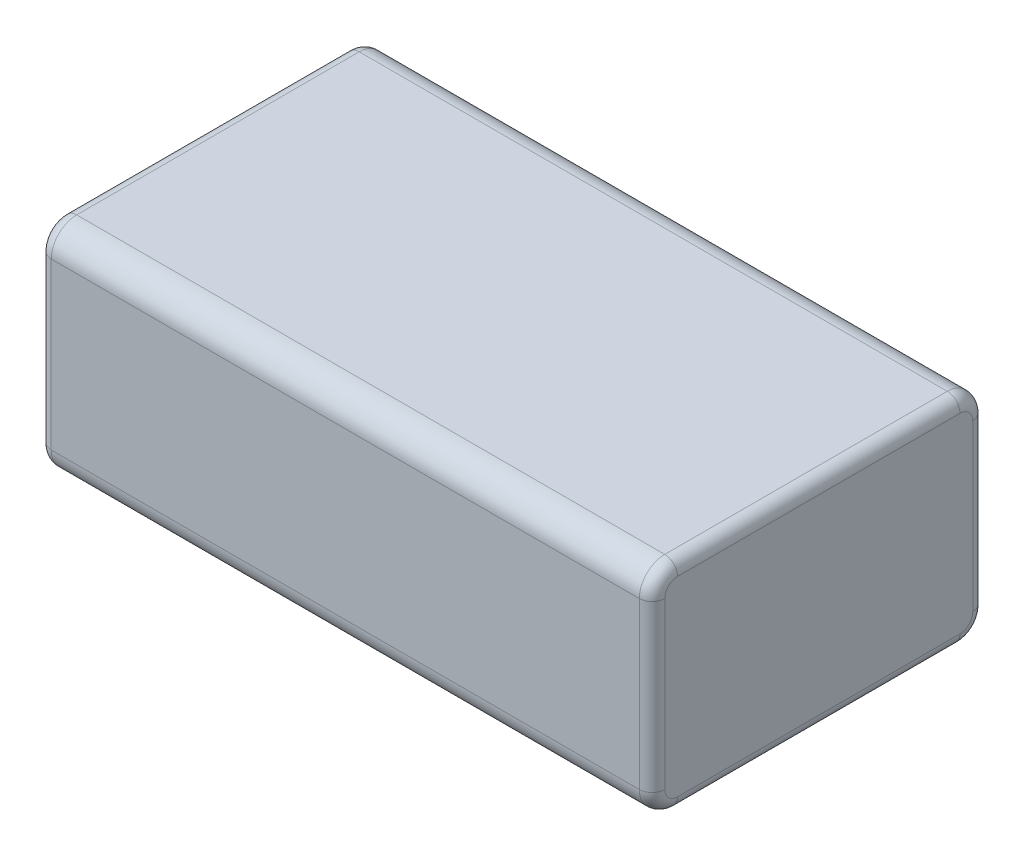
SolidWorks part; units mm, degrees
ref_plane "Front Plane" through (0, 0, 0) normal (0, 0, 1) x (1, 0, 0)
ref_plane "Top Plane" through (0, 0, 0) normal (0, 1, 0) x (1, 0, 0)
ref_plane "Right Plane" through (0, 0, 0) normal (1, 0, 0) x (0, 0, -1)
sketch "Sketch1" plane through (0, 0, 0) normal (0, 1, 0) x (1, 0, 0)
  line L1 (24.075, -13.085) -> (-24.075, -13.085)
  line L2 (24.075, -13.085) -> (24.075, 13.085)
  line L3 (24.075, 13.085) -> (-24.075, 13.085)
  line L4 (-24.075, -13.085) -> (-24.075, 13.085)
  line L5 (24.075, -13.085) -> (-24.075, 13.085) construction
  line L6 (24.075, 13.085) -> (-24.075, -13.085) construction
  point P0 (0, 0)
  dimension "D1" = 48.15
  dimension "D2" = 26.17
extrude "Boss-Extrude1" add sketch "Sketch1" along normal blind 16.98
fillet "Fillet1" radius 2 4 edges at (0, 0, -13.085) (0, 0, 13.085) (0, 16.98, -13.085) (0, 16.98, 13.085)
fillet "Fillet2" radius 1 16 edges at (-24.075, 16.3942, 12.4992) (-24.075, 16.98, 0) (-24.075, 16.3942, -12.4992) (-24.075, 8.49, -13.085) (-24.075, 0.5858, -12.4992) (-24.075, 0, 0) (-24.075, 0.5858, 12.4992) (24.075, 16.3942, 12.4992) (24.075, 16.98, 0) (24.075, 16.3942, -12.4992) (24.075, 8.49, -13.085) (24.075, 0.5858, -12.4992) (24.075, 0, 0) (24.075, 0.5858, 12.4992) (-24.075, 8.49, 13.085) (24.075, 8.49, 13.085)
sketch "Sketch2" plane through (-24.075, 0, 0) normal (-1, 0, 0) x (0, 0, 1)
  line L1 (4.5107, 13.1244) -> (0.6107, 10.8727)
  line L2 (0.6107, 10.8727) -> (0.6107, 6.3694)
  line L3 (0.6107, 6.3694) -> (4.5107, 4.1177)
  line L4 (4.5107, 4.1177) -> (8.4107, 6.3694)
  line L5 (8.4107, 6.3694) -> (8.4107, 10.8727)
  line L6 (8.4107, 10.8727) -> (4.5107, 13.1244)
  circle A0 centre (-5.4512, 8.49) radius 3.665
  circle A1 centre (4.5107, 8.621) radius 3.665
  circle A2 centre (4.5107, 8.621) radius 3.9 construction
  circle A3 centre (-5.4512, 8.49) radius 3.4
  point P12 (0, 0)
  dimension "D1" = 7.33
  dimension "D2" = 7.33
extrude "Boss-Extrude2" add sketch "Sketch2" along normal blind 3
fillet "Fillet6" radius 0.3 7 edges at (-27.075, 8.621, 8.1757) (-27.075, 8.621, 8.4107) (-27.075, 11.9985, 6.4607) (-27.075, 11.9985, 2.5607) (-27.075, 8.621, 0.6107) (-27.075, 5.2435, 6.4607) (-27.075, 5.2435, 2.5607)
fillet "Fillet10" radius 0.1 2 edges at (-27.075, 8.49, -1.7862) (-27.075, 8.49, -2.0512)
